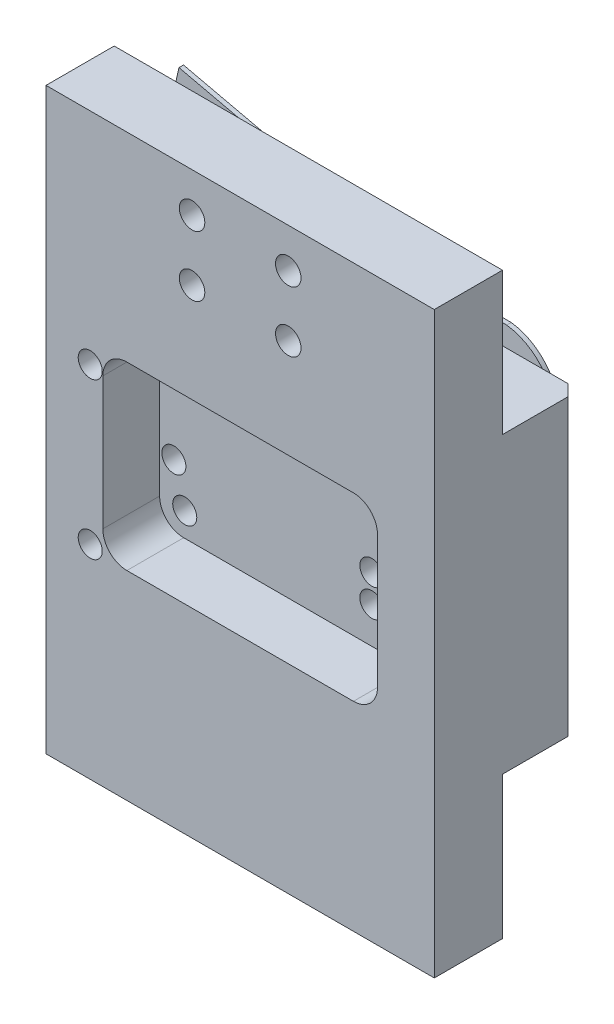
SolidWorks part; units mm, degrees
ref_plane "Alzado" through (0, 0, 0) normal (0, 0, 1) x (1, 0, 0)
ref_plane "Planta" through (0, 0, 0) normal (0, 1, 0) x (1, 0, 0)
ref_plane "Vista lateral" through (0, 0, 0) normal (1, 0, 0) x (0, 0, -1)
sketch "Croquis1" plane through (0, 0, 0) normal (0, 0, 1) x (1, 0, 0)
  line L0 (2788.5159, 1163.0629) -> (2845.3203, 1163.0629)
  line L1 (2857.8614, 1148.5546) -> (2857.8614, 1105.8847)
  line L2 (2857.8614, 1105.8847) -> (2859.7096, 1099.9695)
  line L3 (2859.7096, 1099.9695) -> (2859.7096, 1086.6685)
  line L4 (2859.7096, 1086.6685) -> (2831.925, 1086.6685)
  line L5 (2831.925, 1090.237) -> (2831.925, 1086.6685)
  line L6 (2781.0738, 1094.0948) -> (2827.4673, 1094.0948)
  line L7 (2777.0773, 1099.7185) -> (2777.0773, 1139.3578)
  line L8 (2774.3125, 1143.942) -> (2760.5085, 1156.2703)
  line L9 (2760.5085, 1156.2703) -> (2756.8696, 1168.8846)
  line L10 (2757.8278, 1174.4924) -> (2758.7888, 1178.6707)
  line L11 (2784.8931, 1172.6668) -> (2784.1913, 1169.6153)
  line L12 (2784.8931, 1172.6668) -> (2758.7888, 1178.6707)
  line L13 (2783.6509, 1147.3752) -> (2783.6509, 1106.2537) construction
  arc A0 (2857.8614, 1148.5546) -> (2845.3203, 1163.0629) centre (2843.5531, 1148.8609) ccw
  arc A5 (2831.925, 1090.237) -> (2827.4673, 1094.0948) centre (2827.128, 1089.1983) ccw
  arc A6 (2777.0773, 1099.7185) -> (2781.0738, 1094.0948) centre (2782.0012, 1098.9858) ccw
  arc A7 (2777.0773, 1139.3578) -> (2774.3125, 1143.942) centre (2770.304, 1138.3986) ccw
  arc A8 (2757.8278, 1174.4924) -> (2756.8696, 1168.8846) centre (2764.6187, 1170.4463) ccw
  arc A15 (2784.1913, 1169.6153) -> (2788.5159, 1163.0629) centre (2788.4536, 1167.7251) ccw
  circle A16 centre (2819.6018, 1133.2354) radius 4.4305
  circle A17 centre (2790.7272, 1121.6381) radius 2.0215
  circle A18 centre (2783.6509, 1147.3752) radius 2.8722
  circle A19 centre (2793.6078, 1111.4193) radius 2.6807
  circle A20 centre (2783.6509, 1106.2537) radius 2.8722
  circle A22 centre (2842.9135, 1132.266) radius 2.7764
  circle A23 centre (2843.0093, 1122.0339) radius 2.1062
  circle A24 centre (2843.0093, 1114.6706) radius 2.7904
  point P0 (0, 0)
extrude "Saliente-Extruir1" add sketch "Croquis1" along normal blind 1.19
ref_plane "Plano1" through (0, 0, 11.19) normal (0, 0, 1) x (1, 0, 0)
sketch "Croquis7" plane through (0, 0, 11.19) normal (0, 0, 1) x (1, 0, 0)
  line L0 (2777.0773, 1139.3578) -> (2777.0773, 1099.7185) construction
  line L1 (2771.9773, 1090.0948) -> (2874.4973, 1090.0948)
  line L2 (2771.9773, 1090.0948) -> (2771.9773, 1167.7648)
  line L3 (2771.9773, 1167.7648) -> (2874.4973, 1167.7648)
  line L4 (2874.4973, 1090.0948) -> (2874.4973, 1167.7648)
  line L5 (2781.0738, 1094.0948) -> (2827.4673, 1094.0948) construction
  dimension "D1" = 102.52
  dimension "D2" = 77.67
  dimension "D3" = 5.1
  dimension "D4" = 4
extrude "Saliente-Extruir2" add sketch "Croquis7" along normal blind 38.3 separate body
sketch "Croquis8" plane through (0, 0, 11.19) normal (0, 0, -1) x (-1, 0, 0)
  circle A0 centre (-2783.6509, 1106.2537) radius 3.175
  circle A1 centre (-2783.6509, 1147.3752) radius 3.175
  circle A2 centre (-2790.7272, 1121.6381) radius 2.0215
  circle A3 centre (-2793.6078, 1111.4193) radius 2.6807
  circle A4 centre (-2819.6018, 1133.2354) radius 4.4305
  circle A5 centre (-2842.9135, 1132.266) radius 2.7764
  circle A6 centre (-2843.0093, 1122.0339) radius 2.1062
  circle A7 centre (-2843.0093, 1114.6706) radius 2.7904
  dimension "D1" = 41.1215
  dimension "D2" = 6.35
sketch "Croquis9" plane through (0, 0, 49.49) normal (0, 0, 1) x (1, 0, 0)
  line L0 (2771.9773, 1167.7648) -> (2771.9773, 1090.0948) construction
  line L1 (2874.4973, 1205.3568) -> (2771.9773, 1205.3568)
  line L2 (2874.4973, 1205.3568) -> (2874.4973, 1052.5028)
  line L3 (2874.4973, 1052.5028) -> (2771.9773, 1052.5028)
  line L4 (2771.9773, 1205.3568) -> (2771.9773, 1052.5028)
  line L5 (2874.4973, 1205.3568) -> (2771.9773, 1052.5028) construction
  line L6 (2874.4973, 1052.5028) -> (2771.9773, 1205.3568) construction
  line L7 (2771.9773, 1090.0948) -> (2874.4973, 1090.0948) construction
  point P0 (2823.2373, 1128.9298)
  point P8 (2771.9773, 1128.9298)
  point P12 (2823.2373, 1090.0948)
  dimension "D1" = 37.592
extrude "Saliente-Extruir3" add sketch "Croquis9" against normal blind 18
sketch "Croquis10" plane through (0, 0, 49.49) normal (0, 0, 1) x (1, 0, 0)
  line L0 (2874.4973, 1052.5028) -> (2874.4973, 1205.3568) construction
  line L1 (2786.9773, 1152.7648) -> (2859.4973, 1152.7648)
  line L2 (2786.9773, 1152.7648) -> (2786.9773, 1105.0948)
  line L3 (2786.9773, 1105.0948) -> (2859.4973, 1105.0948)
  line L4 (2859.4973, 1152.7648) -> (2859.4973, 1105.0948)
  line L5 (2786.9773, 1152.7648) -> (2859.4973, 1105.0948) construction
  line L6 (2786.9773, 1105.0948) -> (2859.4973, 1152.7648) construction
  line L7 (2771.9773, 1205.3568) -> (2771.9773, 1052.5028) construction
  point P0 (2823.2373, 1128.9298)
  dimension "D1" = 15
  dimension "D2" = 15
  dimension "D3" = 15
  dimension "D4" = 15
extrude "Cortar-Extruir2" cut sketch "Croquis10" against normal blind 15
extrude "Cortar-Extruir3" cut sketch "Croquis8" against normal through all contours A2 | A6 | A7 | A3
fillet "Redondeo1" radius 6.35 4 edges at (2786.9773, 1152.7648, 41.99) (2859.4973, 1152.7648, 41.99) (2859.4973, 1105.0948, 41.99) (2786.9773, 1105.0948, 41.99)
extrude "Cortar-Extruir4" cut sketch "Croquis8<7>" against normal up to surface (38.3 mm away) contours A1 | A0 up to face at (2823.2373, 1128.9298, 49.49)
sketch "Croquis8<7>" plane through (0, 0, 11.19) normal (0, 0, -1) x (-1, 0, 0) same geometry as "Croquis8"
sketch "Croquis11" plane through (0, 0, 34.49) normal (0, 0, 1) x (1, 0, 0)
  circle A0 centre (2843.0093, 1114.6706) radius 3.175
  circle A1 centre (2843.0093, 1122.0339) radius 3.175
  circle A2 centre (2790.7272, 1121.6381) radius 3.175
  circle A3 centre (2793.6078, 1111.4193) radius 3.175
  point P12 (0, 0)
  dimension "D1" = 6.35
extrude "Cortar-Extruir5" cut sketch "Croquis11" against normal blind 5 contours A1 | A2
chamfer "Chaflán1" distance 3 angle 45 1 edges at (2874.4973, 1128.9298, 11.19)
sketch "Croquis12" plane through (0, 0, 31.49) normal (0, 0, -1) x (-1, 0, 0)
  line L0 (-2835.9373, 1194.9428) -> (-2810.5373, 1194.9428) construction
  line L1 (-2874.4973, 1205.3568) -> (-2771.9773, 1205.3568) construction
  line L2 (-2835.9373, 1178.9408) -> (-2810.5373, 1178.9408) construction
  line L3 (-2835.9373, 1178.9408) -> (-2835.9373, 1194.9428) construction
  circle A0 centre (-2835.9373, 1194.9428) radius 3.3655
  circle A1 centre (-2835.9373, 1178.9408) radius 3.3655
  circle A2 centre (-2810.5373, 1178.9408) radius 3.3655
  circle A3 centre (-2810.5373, 1194.9428) radius 3.3655
  point P8 (-2823.2373, 1194.9428)
  point P11 (-2823.2373, 1205.3568)
  dimension "D5" = 6.731
  dimension "D1" = 25.4
  dimension "D2" = 16.002
  dimension "D3" = 25.4
  dimension "D4" = 16.002
  dimension "D6" = 25.4
  dimension "D7" = 16.002
  dimension "D8" = 10.414
extrude "Cortar-Extruir6" cut sketch "Croquis12" against normal through all and the other way through all
sketch "Croquis13" plane through (0, 0, 31.49) normal (0, 0, -1) x (-1, 0, 0)
  line L0 (-2874.4973, 1205.3568) -> (-2771.9773, 1205.3568) construction
  line L1 (-2807.4893, 1202.8168) -> (-2838.9853, 1202.8168)
  line L2 (-2804.1873, 1199.5148) -> (-2804.1873, 1174.3688)
  line L3 (-2807.4893, 1171.0668) -> (-2838.9853, 1171.0668)
  line L4 (-2842.2873, 1199.5148) -> (-2842.2873, 1174.3688)
  line L5 (-2810.5373, 1178.9408) -> (-2810.5373, 1194.9428) construction
  arc A0 (-2838.9853, 1171.0668) -> (-2842.2873, 1174.3688) centre (-2838.9853, 1174.3688) cw
  arc A1 (-2838.9853, 1202.8168) -> (-2842.2873, 1199.5148) centre (-2838.9853, 1199.5148) ccw
  arc A2 (-2804.1873, 1174.3688) -> (-2807.4893, 1171.0668) centre (-2807.4893, 1174.3688) cw
  arc A3 (-2807.4893, 1202.8168) -> (-2804.1873, 1199.5148) centre (-2807.4893, 1199.5148) cw
  point P6 (-2823.2373, 1202.8168)
  point P7 (-2823.2373, 1205.3568)
  point P12 (-2810.5373, 1186.9418)
  point P13 (-2804.1873, 1186.9418)
  point P18 (-2842.2873, 1202.8168)
  point P21 (-2804.1873, 1171.0668)
  point P24 (-2804.1873, 1202.8168)
  dimension "D3" = 3.302
  dimension "D1" = 31.75
  dimension "D2" = 38.1
extrude "Cortar-Extruir7" cut sketch "Croquis13" against normal blind 3.0988
extrude "Cortar-Extruir8" cut sketch "Croquis11<5>" against normal through all contours A0 | A3
sketch "Croquis11<5>" plane through (0, 0, 34.49) normal (0, 0, 1) x (1, 0, 0) same geometry as "Croquis11"
